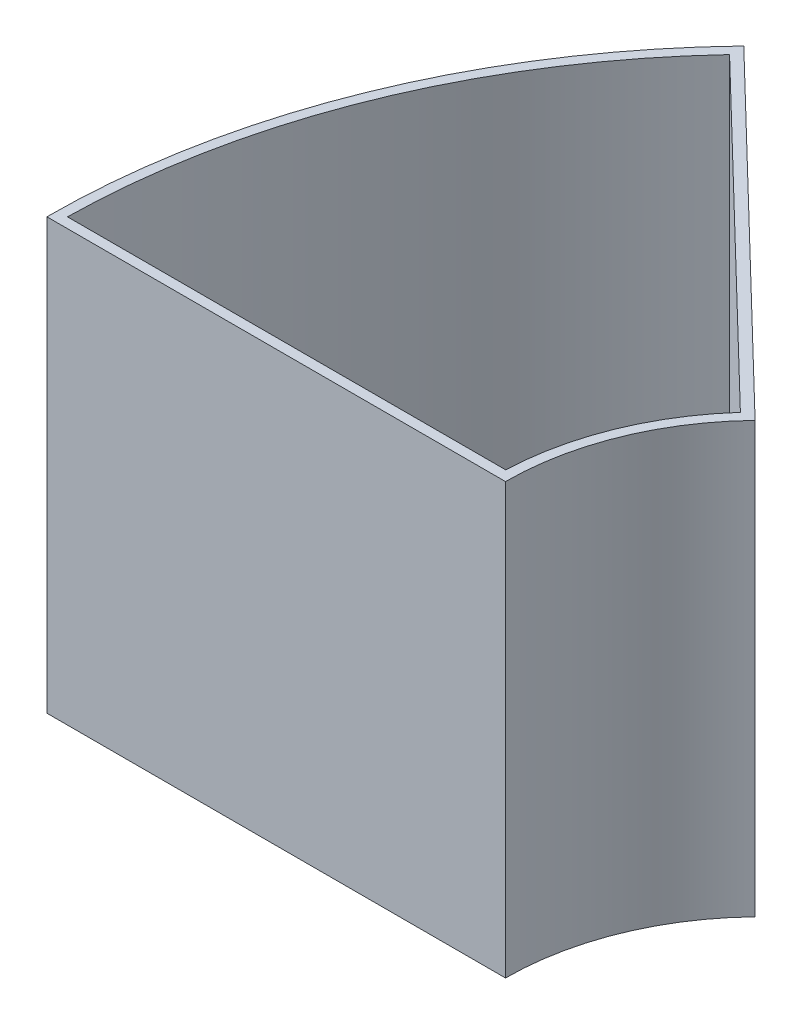
SolidWorks part; units mm, degrees
ref_plane "Alzado" through (0, 0, 0) normal (0, 0, 1) x (1, 0, 0)
ref_plane "Planta" through (0, 0, 0) normal (0, 1, 0) x (1, 0, 0)
ref_plane "Vista lateral" through (0, 0, 0) normal (1, 0, 0) x (0, 0, -1)
sketch "Croquis1" plane through (0, 0, 0) normal (0, 1, 0) x (1, 0, 0)
  line L0 (0, 0) -> (-75, 0) construction
  line L1 (0, 0) -> (-50.2099, 48.4872) construction
  line L2 (-25, 0) -> (-69.8, 0)
  line L4 (-50.2099, 48.4872) -> (-17.9835, 17.3665)
  circle A0 centre (0, 0) radius 75 construction
  circle A1 centre (0, 0) radius 69.8 construction
  circle A2 centre (0, 0) radius 25 construction
  arc A3 (-25, 0) -> (-17.9835, 17.3665) centre (0, 0) cw
  arc A4 (-69.8, 0) -> (-50.2099, 48.4872) centre (0, 0) cw
  dimension "D1" = 150
  dimension "D2" = 5.2
  dimension "D3" = 50
  dimension "D4" = 44
extrude "Saliente-Extruir1" add sketch "Croquis1" along normal blind 40
shell "Vaciado1" thickness 1 removed face at (-42.3484, 40, -17.1099)
sketch "Croquis4" plane through (0, 0, 0) normal (0, -1, 0) x (1, 0, 0)
  line L0 (-25, 0) -> (-69.8, 0)
  line L1 (-17.9835, -17.3665) -> (-50.2099, -48.4872)
  arc A0 (-69.8, 0) -> (-50.2099, -48.4872) centre (0, 0) ccw
  arc A1 (-25, 0) -> (-17.9835, -17.3665) centre (0, 0) ccw
extrude "Saliente-Extruir3" add sketch "Croquis4" along normal blind 2
sketch "Croquis5" plane through (0, 1, 0) normal (0, 1, 0) x (1, 0, 0)
  line L0 (0, 0) -> (-64.7174, 26.1475) construction
  arc A1 (-50.2099, 48.4872) -> (-69.8, 0) centre (0, 0) ccw construction
  circle A2 centre (-55.631, 22.4764) radius 3.75
  dimension "D1" = 7.5
  dimension "D2" = 60
extrude "Cortar-Extruir2" cut sketch "Croquis5" against normal blind 2.5
sketch "Croquis6" plane through (0, 1, 0) normal (0, 1, 0) x (1, 0, 0)
  line L1 (-25, 0) -> (-50, 0)
  line L3 (-17.9835, 17.3665) -> (-35.967, 34.7329)
  line L4 (-17.9835, 17.3665) -> (-50.2099, 48.4872) construction
  circle A0 centre (0, 0) radius 50 construction
  arc A1 (-25, 0) -> (-17.9835, 17.3665) centre (0, 0) cw
  arc A3 (-50, 0) -> (-35.967, 34.7329) centre (0, 0) cw
  dimension "D1" = 100
extrude "Saliente-Extruir5" add sketch "Croquis6" along normal blind 5
sketch "Croquis2" plane through (0, -2, 0) normal (0, 1, 0) x (1, 0, 0)
  line L0 (-39.7289, 27.8185) -> (-29.899, 20.9355)
  line L1 (-47.9029, 7.5871) -> (-36.0506, 5.7099)
  line L2 (-17.9835, 17.3665) -> (-50.2099, 48.4872) construction
  circle A0 centre (0, 0) radius 36.5 construction
  circle A1 centre (0, 0) radius 48.5 construction
  arc A2 (-36.0506, 5.7099) -> (-29.899, 20.9355) centre (0, 0) cw
  arc A3 (-47.9029, 7.5871) -> (-39.7289, 27.8185) centre (0, 0) cw
  dimension "D1" = 73
  dimension "D2" = 97
  dimension "D3" = 9
  dimension "D4" = 26
extrude "Cortar-Extruir3" cut sketch "Croquis2" along normal blind 6
